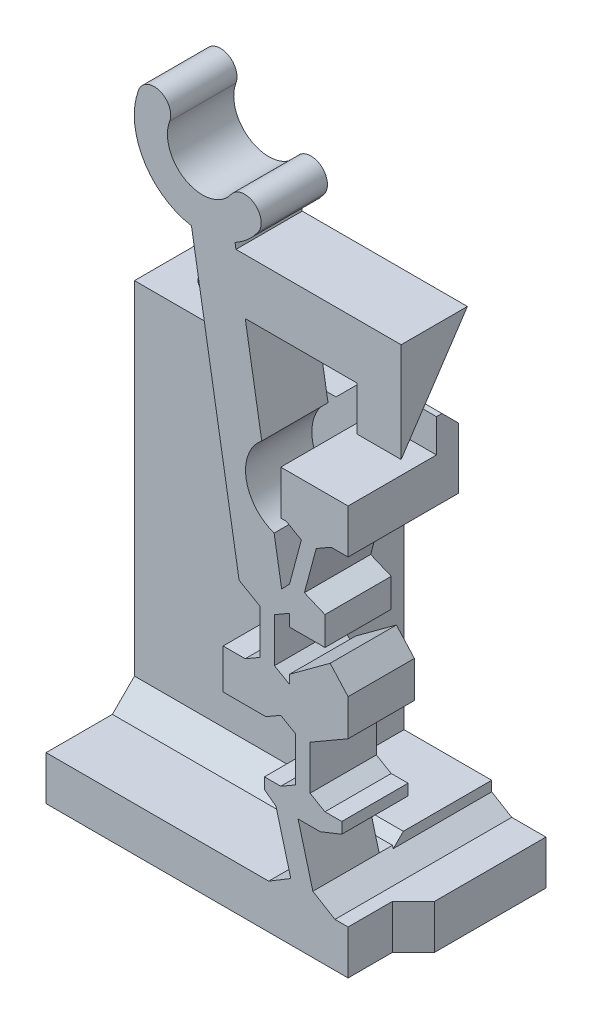
SolidWorks part; units mm, degrees
material "Nylon 6/12"
ref_plane "Front Plane" through (0, 0, 0) normal (0, 0, 1) x (1, 0, 0)
ref_plane "Top Plane" through (0, 0, 0) normal (0, 1, 0) x (1, 0, 0)
ref_plane "Right Plane" through (0, 0, 0) normal (1, 0, 0) x (0, 0, -1)
sketch "Sketch-SkeletonConfigUp" plane through (0, 0, 0) normal (0, 0, 1) x (1, 0, 0)
  line L0 (0, 0) -> (0, -50000) construction
  line L1 (0, 0) -> (4.5811, 6.2164) construction
  line L2 (9.8143, 13.3177) -> (4.5811, 13.945) construction
  line L3 (4.5811, 13.945) -> (2.9713, 10.4094) construction
  line L4 (2.9713, 10.4094) -> (4.5811, 6.2164) construction
  line L5 (4.5811, 13.945) -> (6.2429, 19.1409) construction
  line L6 (2.9713, 10.4094) -> (0.0405, 27.8193) construction
  line L7 (4.5811, 6.2164) -> (9.8143, 13.3177) construction
  line L8 (-587.3593, -797.0242) -> (9.8143, 13.3177) construction
  dimension "D2" = 7.7221
  dimension "D3" = 8.8212
  dimension "D4" = 5.2707
  dimension "D5" = 119.553
  dimension "D6" = 3.8848
  dimension "D7" = 5.4552
  dimension "D8" = 17.6549
  dimension "D9" = 4.4914
  dimension "D10" = 6.745
  dimension "D11" = 145.964
  dimension "D12" = 143.612
sketch "Sketch-SkeletonConfigDown" plane through (0, 0, 0) normal (0, 0, 1) x (1, 0, 0)
  line L0 (0, 0) -> (0, -50000) construction
  line L1 (0, 0) -> (4.5811, 6.2164) construction
  line L2 (9.8143, 13.3177) -> (4.5811, 13.945) construction
  line L3 (4.5811, 13.945) -> (6.1909, 10.4094) construction
  line L4 (6.1909, 10.4094) -> (4.5811, 6.2164) construction
  line L5 (4.5811, 13.945) -> (1.753, 18.6098) construction
  line L6 (6.1909, 10.4094) -> (-8.8652, 19.6294) construction
  line L7 (4.5811, 6.2164) -> (9.8143, 13.3177) construction
  line L8 (-589.9357, -800.5203) -> (9.8143, 13.3177) construction
  dimension "D2" = 7.7221
  dimension "D3" = 8.8212
  dimension "D4" = 5.2707
  dimension "D5" = 119.553
  dimension "D6" = 3.8848
  dimension "D7" = 5.4552
  dimension "D8" = 17.6549
  dimension "D9" = 4.4914
  dimension "D10" = 6.745
  dimension "D11" = 145.964
  dimension "D1" = 143.612
ref_plane "Plane-Cam Base" through (9.128, 0, 0) normal (1, 0, 0) x (0, 0, -1)
ref_plane "Plane-Down-to-Up Derailleur Clearance" through (6.628, 0, 0) normal (1, 0, 0) x (0, 0, -1)
ref_plane "Plane-Cam Cavity Roof" through (5.128, 0, 0) normal (1, 0, 0) x (0, 0, -1)
sketch "Sketch-SwitchBossUp" plane through (0, 0, 0) normal (0, 0, 1) x (1, 0, 0)
  line L0 (3.5811, 11.4759) -> (3.5811, 12.945) construction
  line L5 (5.5811, 12.5552) -> (5.5811, 11.263)
  line L7 (1.5115, 25.1048) -> (1.5536, 24.8548)
  line L8 (-0.4607, 24.7728) -> (1.6966, 11.9577)
  line L9 (2.9713, 10.4094) -> (0.0405, 27.8193) construction
  line L11 (0.1364, 21.2256) -> (2.1086, 21.5576) construction
  line L15 (6.628, -23.7286) -> (6.628, 23.7286) construction
  line L16 (2.9713, 10.4094) -> (4.5811, 6.2164) construction
  line L17 (3.5811, 12.945) -> (3.5811, 14.945) construction
  line L18 (5.5811, 12.945) -> (5.5811, 14.945) construction
  line L19 (4.2561, 13.945) -> (4.9061, 13.945) construction
  line L20 (3.5811, 14.945) -> (5.5811, 14.945) construction
  line L21 (3.5811, 12.945) -> (5.5811, 12.945) construction
  line L22 (4.5811, 12.945) -> (4.5811, 14.945) construction
  line L23 (4.5811, 6.2164) -> (8.5405, 7.1023) construction
  line L24 (1.9713, 9.4094) -> (1.9713, 11.4094) construction
  line L25 (3.9713, 9.4094) -> (3.9713, 11.4094) construction
  line L26 (3.9713, 9.4094) -> (1.9713, 9.4094) construction
  line L27 (1.9713, 11.4094) -> (3.9713, 11.4094) construction
  line L28 (3.5811, 7.2164) -> (5.5811, 7.2164) construction
  line L29 (3.5811, 7.2164) -> (3.5811, 5.2164) construction
  line L30 (5.5811, 7.2164) -> (5.5811, 5.2164) construction
  line L31 (3.5811, 5.2164) -> (5.5811, 5.2164) construction
  line L32 (4.9061, 6.2164) -> (4.2561, 6.2164) construction
  line L40 (3.2963, 10.4094) -> (2.6463, 10.4094) construction
  line L66 (0.0405, 27.8193) -> (0.0405, 50027.8193) construction
  line L76 (5.5811, 11.263) -> (5.5811, 12.5552) construction
  line L77 (5.5811, 7.6061) -> (6.628, 8.2105)
  line L80 (5.8152, 10.763) -> (6.628, 9.8603)
  line L81 (9.128, 1033.2419) -> (9.128, 20.0586) construction
  line L85 (6.9307, 9.5241) -> (8.5405, 7.7363) construction
  line L88 (5.7256, 17.3347) -> (6.628, 17.3347)
  line L92 (3.7762, 8.3129) -> (6.9307, 9.5241) construction
  line L98 (1.9713, 9.0197) -> (0.9713, 9.0197)
  line L99 (0.9713, 9.0197) -> (0.9713, 7.2164)
  line L100 (0.9713, 7.2164) -> (2.9061, 7.2164)
  line L101 (4.5811, 6.2164) -> (6.9307, 9.5241) construction
  line L103 (0.0405, 27.8193) -> (1.9448, 26.4638) construction
  line L104 (6.9307, 9.5241) -> (8.5405, 7.7363) construction
  line L107 (1.9713, 9.4094) -> (1.9713, 9.0197) construction
  line L109 (0.0405, 27.8193) -> (-2.1498, 28.6358) construction
  line L111 (6.628, 9.8603) -> (6.628, 8.2105)
  line L112 (6.628, 9.8603) -> (6.9307, 9.5241) construction
  line L113 (2.8424, 4.8267) -> (2.8424, 4.3267)
  line L114 (7.3693, 7.7363) -> (7.3563, 7.7363) construction
  line L121 (5.0345, -1.1653) -> (5.0345, 1.437) construction
  line L122 (9.028, 22.3548) -> (9.028, 20.3548)
  line L127 (5.5811, 15.3347) -> (5.5811, 14.945) construction
  line L130 (6.0345, 0.8347) -> (6.628, 0.8347)
  line L132 (2.8424, 4.3267) -> (3.3646, 3.937)
  line L133 (2.9713, 10.4094) -> (6.1909, 10.4094) construction
  line L134 (4.5811, 10.4094) -> (4.5811, 13.945) construction
  line L135 (4.5811, 10.4094) -> (4.5811, 6.2164) construction
  line L137 (3.9713, 9.4094) -> (5.5811, 7.2164) construction
  line L139 (5.8152, 10.763) -> (3.9713, 9.4094)
  line L141 (4.0345, 1.437) -> (3.0345, 0.8347)
  line L142 (3.0345, 0.8347) -> (3.0345, -1.1653)
  line L143 (9.128, 20.0586) -> (9.128, 18.3333) construction
  line L145 (9.128, 16.6071) -> (9.128, -49992.4167) construction
  line L147 (5.5811, 11.263) -> (5.5811, 12.5552) construction
  line L150 (3.0345, -1.1653) -> (5.0345, -1.1653)
  line L151 (3.3646, 3.937) -> (4.3646, 3.937) construction
  line L152 (4.5126, 14.945) -> (3.9767, 12.945)
  line L153 (5.1855, 14.945) -> (4.6496, 12.945)
  line L157 (3.5811, 17.3347) -> (3.5811, 15.3347)
  line L158 (5.8605, 15.3347) -> (6.628, 15.3347)
  line L162 (3.2963, 11.4094) -> (3.2963, 9.4094)
  line L164 (2.6463, 11.4094) -> (2.6463, 9.4094)
  line L169 (4.2561, 7.2164) -> (4.2561, 5.2164)
  line L170 (4.9061, 5.2164) -> (4.9061, 7.2164)
  line L175 (4.2561, 7.2164) -> (3.5811, 7.6061)
  line L176 (4.9061, 7.2164) -> (5.5811, 7.6061)
  line L177 (5.5811, 7.2164) -> (5.5811, 7.6061) construction
  line L179 (4.2561, 5.2164) -> (3.5811, 4.8267)
  line L180 (3.5811, 5.2164) -> (3.5811, 4.8267) construction
  line L181 (3.5811, 4.8267) -> (2.8424, 4.8267)
  line L183 (4.9061, 5.2164) -> (5.5811, 4.8267)
  line L184 (5.5811, 5.2164) -> (5.5811, 4.8267) construction
  line L186 (9.128, -23.7286) -> (9.128, 23.7286) construction
  line L187 (2.6463, 9.4094) -> (1.9713, 9.0197)
  line L188 (3.2963, 9.4094) -> (3.9713, 9.0197)
  line L189 (3.2963, 11.4094) -> (3.9713, 11.7991)
  line L190 (2.6463, 11.4094) -> (1.6966, 11.9577)
  line L191 (3.9713, 11.4094) -> (3.9713, 11.7991) construction
  line L192 (3.9713, 11.7991) -> (3.9713, 11.263)
  line L193 (4.6496, 12.945) -> (5.5811, 12.5552)
  line L194 (3.9767, 12.945) -> (3.6203, 12.5779)
  line L195 (3.9713, 11.263) -> (5.5811, 11.263)
  line L196 (3.9713, 9.4094) -> (3.9713, 9.0197)
  line L197 (3.5811, 7.2164) -> (3.5811, 7.6061) construction
  line L199 (3.5811, 7.6061) -> (2.9061, 7.2164)
  line L201 (2.8424, 4.3267) -> (2.8424, 3.937) construction
  line L202 (2.8424, 3.937) -> (3.3646, 3.937) construction
  line L204 (5.0345, 1.437) -> (3.0345, 1.437) construction
  line L205 (3.0345, 1.437) -> (3.0345, 0.8347) construction
  line L206 (5.0345, 1.437) -> (6.0345, 0.8347)
  line L207 (9.128, 18.3333) -> (9.128, 16.6071) construction
  line L208 (6.628, -1.1653) -> (6.628, 0.8347)
  line L209 (9.128, 20.0586) -> (9.128, 16.6071) construction
  line L211 (5.0345, 1.437) -> (4.3646, 3.937)
  line L212 (4.0345, 1.437) -> (3.3646, 3.937)
  line L214 (4.5126, 14.945) -> (3.8375, 15.3347)
  line L215 (3.8375, 15.3347) -> (3.5811, 15.3347)
  line L216 (5.1855, 14.945) -> (5.8605, 15.3347)
  line L217 (5.5811, 12.945) -> (5.5811, 12.5552) construction
  line L218 (5.1855, 14.945) -> (5.1855, 15.3347) construction
  line L219 (5.8605, 15.3347) -> (3.8375, 15.3347) construction
  line L221 (9.028, 22.3548) -> (9.028, 24.8548)
  line L224 (3.5811, 17.3347) -> (5.7256, 17.3347)
  line L232 (6.628, 15.3347) -> (6.628, 17.3347)
  line L233 (6.628, -1.1653) -> (5.0345, -1.1653)
  line L236 (1.5536, 24.8548) -> (9.028, 24.8548)
  line L240 (4.3646, 3.937) -> (5.3646, 3.937)
  line L241 (5.3646, 3.937) -> (6.3424, 4.3267)
  line L248 (7.028, 22.3548) -> (1.9744, 22.3548)
  line L249 (1.9744, 22.3548) -> (2.7198, 17.9273)
  line L250 (9.028, 20.3548) -> (7.028, 20.3548)
  line L251 (7.028, 20.3548) -> (7.028, 22.3548)
  line L252 (3.2801, 14.5986) -> (3.6203, 12.5779)
  line L253 (4.2672, 14.0291) -> (4.895, 13.8608) construction
  line L367 (5.5811, 4.8267) -> (6.3424, 4.8267)
  line L368 (6.3424, 4.8267) -> (6.3424, 4.3267)
  arc A0 (1.5115, 25.1048) -> (2.5558, 26.0289) centre (0.0405, 27.8193) ccw
  arc A1 (-0.4607, 24.7728) -> (-2.8525, 28.8978) centre (0.0405, 27.8193) cw
  arc A2 (-2.8525, 28.8978) -> (-1.447, 28.3738) centre (-2.1498, 28.6358) cw
  arc A3 (2.5558, 26.0289) -> (1.3338, 26.8987) centre (1.9448, 26.4638) ccw
  arc A4 (-1.447, 28.3738) -> (1.3338, 26.8987) centre (0.0405, 27.8193) ccw
  arc A5 (3.5811, 12.945) -> (3.5811, 14.945) centre (3.1778, 13.945) ccw construction
  arc A6 (5.5811, 12.945) -> (5.5811, 14.945) centre (5.9843, 13.945) cw construction
  arc A7 (2.5293, 9.921) -> (1.9713, 11.4094) centre (1.568, 10.4094) ccw construction
  arc A8 (3.9713, 11.4094) -> (3.9713, 9.4094) centre (4.3745, 10.4094) ccw construction
  arc A9 (3.5811, 7.2164) -> (3.5811, 5.2164) centre (3.1779, 6.2164) cw construction
  arc A10 (5.5811, 7.2164) -> (5.5811, 5.2164) centre (5.9844, 6.2164) ccw construction
  circle A28 centre (0.0405, 27.8193) radius 2.3375 construction
  arc A29 (1.9713, 9.4094) -> (2.5293, 9.921) centre (1.568, 10.4094) ccw construction
  arc A30 (3.2801, 14.5986) -> (2.7198, 17.9273) centre (3.9114, 16.4164) cw
  point P53 (4.5811, 13.945)
  point P63 (2.9713, 10.4094)
  point P80 (0, 0)
  point P83 (0, 0)
  point P93 (1.1225, 21.3916)
  dimension "D23" = 1.5875
  dimension "D24" = 0.75
  dimension "D2" = 2
  dimension "D5" = 2
  dimension "D8" = 42
  dimension "D16" = 42
  dimension "D27" = 120
  dimension "D28" = 120
  dimension "D29" = 120
  dimension "D30" = 120
  dimension "D31" = 120
  dimension "D32" = 120
  dimension "D33" = 120
  dimension "D34" = 120
  dimension "D17" = 0.5
  dimension "D21" = 2
  dimension "D22" = 1
  dimension "D38" = 2
  dimension "D39" = 0.5
  dimension "D40" = 60
  dimension "D41" = 1
  dimension "D42" = 45
  dimension "D43" = 120
  dimension "D10" = 15
  dimension "D12" = 2.5
  dimension "D13" = 1
  dimension "D19" = 1
  dimension "D25" = 15
  dimension "D26" = 120
  dimension "D35" = 120
  dimension "D20" = 3
  dimension "D48" = 2
  dimension "D82" = 1
  dimension "D83" = 3.5
  dimension "D14" = 2.5
  dimension "D15" = 0.25
  dimension "D7" = 2
  dimension "D9" = 2
  dimension "D6" = 0.65
extrude "Boss-Switch Body" add sketch "Sketch-SwitchBossUp" along normal blind 3
sketch "Sketch1" plane through (0, 0, 0) normal (0, 0, -1) x (-1, 0, 0)
  line L1 (-7.5811, -1.1653) -> (0.4122, -1.1653)
  line L2 (-7.5811, -1.1653) -> (-7.5811, 0.8347)
  line L4 (0.4122, -1.1653) -> (0.4122, 0.8347)
  line L5 (-3.5811, 18.8347) -> (-7.5811, 18.8347)
  line L10 (-7.5811, 18.8347) -> (-7.5811, 15.3347)
  line L11 (-4.0345, 1.437) -> (-5.0345, 1.437)
  line L12 (-7.5811, 15.3347) -> (-3.5811, 15.3347)
  line L13 (-4.0345, 1.437) -> (-3.0345, 0.8347)
  line L14 (-3.5811, 15.3347) -> (-3.5811, 18.8347)
  line L20 (-4.3646, 3.937) -> (-5.0345, 1.437) construction
  line L22 (-3.0345, -1.1653) -> (-6.628, -1.1653) construction
  line L23 (-3.0345, 0.8347) -> (0.4122, 0.8347)
  line L24 (-5.0345, 1.437) -> (-6.0345, 0.8347)
  line L25 (-6.0345, 0.8347) -> (-7.5811, 0.8347)
  dimension "D1" = 3.5
extrude "Boss-Flange Width" add sketch "Sketch1" along normal blind 5
ref_plane "Plane-Sta2Sit Groove" through (0.0405, 0, 0) normal (1, 0, 0) x (0, 0, -1)
ref_plane "Plane-Cam Outer Surface" through (-12.0395, 0, 0) normal (1, 0, 0) x (0, 0, -1)
ref_plane "Plane-FlangeTop" through (-7.0395, 0, 0) normal (1, 0, 0) x (0, 0, -1)
sketch "Sketch2" plane through (-7.0395, 0, 0) normal (1, 0, 0) x (0, 0, -1)
  line L0 (5, 15.3347) -> (-3, 15.3347) construction
  line L1 (5, 17.3347) -> (1, 17.3347)
  line L2 (5, 17.3347) -> (5, 15.3347)
  line L3 (5, 15.3347) -> (1, 15.3347)
  line L4 (1, 17.3347) -> (1, 15.3347)
  line L5 (-3, -1.1653) -> (-3, 0.8347) construction
  line L11 (5, 0.8347) -> (-3, 0.8347)
  line L12 (5, 0.8347) -> (5, -1.1653)
  line L13 (5, -1.1653) -> (-3, -1.1653)
  line L14 (-3, 0.8347) -> (-3, -1.1653)
  line L15 (0, 10.4094) -> (0, 27.8193) construction
  line L17 (5, 0.8347) -> (5, -1.1653) construction
  line L18 (-3, 0.8347) -> (0, 0.8347) construction
  dimension "D1" = 1
  dimension "D2" = 2
extrude "Boss-Flange Height" add sketch "Sketch2" along normal up to surface (11.6675 mm away)
sketch "Sketch10" plane through (0, 15.3347, 0) normal (0, 1, 0) x (1, 0, 0)
  line L0 (9.128, -23.7286) -> (9.128, 23.7286) construction
  line L1 (7.5811, 5) -> (5.128, 5)
  line L2 (7.5811, 5) -> (7.5811, 2)
  line L3 (7.5811, 2) -> (5.128, 2)
  line L5 (4.628, 7) -> (4.628, 1) construction
  line L6 (3.5811, 1) -> (-7.0395, 1) construction
  line L8 (5.128, 5) -> (5.128, 2)
  dimension "D1" = 1
  dimension "D2" = 0.5
  dimension "D3" = 4.5
extrude "Cut-Up-To-Down Derailleur Clearance" cut sketch "Sketch10" along normal up to next
sketch "Sketch17" plane through (0, 15.3347, 0) normal (0, -1, 0) x (1, 0, 0)
  line L0 (5.128, -5) -> (-7.0395, -5)
  line L1 (5.128, -5) -> (-7.0395, -5) construction
  line L2 (-7.0395, -5) -> (-7.0395, -1)
  line L3 (-7.0395, -1) -> (5.128, -1)
  line L4 (5.128, -1) -> (5.128, -5)
  line L5 (-7.0395, -1) -> (-7.0395, -5) construction
extrude "Boss-Flange Support" add sketch "Sketch17" along normal up to surface (14.5 mm away) up to face at (-2.0025, 0.8347, -1)
sketch "Sketch-HolePositions" plane through (0, -1.1653, 0) normal (0, -1, 0) x (1, 0, 0)
  line L0 (-7.0395, -3) -> (7.5811, -3) construction
  line L1 (7.5811, -5) -> (-7.0395, -5) construction
  line L2 (7.5811, -5) -> (7.5811, 0) construction
  line L4 (-7.0395, -22.2167) -> (-7.0395, 22.2167) construction
  point P6 (-5.0395, -3)
  point P7 (-0.5395, -3)
  dimension "D1" = 2
  dimension "D2" = 4.5
  dimension "D3" = 2
sketch "Sketch6" plane through (0, -1.1653, 0) normal (0, -1, 0) x (-1, 0, 0)
  point P0 (5.0395, 3)
  point P3 (0.5395, 3)
hole_wizard "Tap Drill for M2x0.4 Tap1" positions "Sketch6" profile "Sketch5" hole size "M2x0.4" standard "ANSI Metric" end condition through all
sketch "Sketch5" plane through (-5.0395, -1.1653, -3) normal (1, 0, 0) x (0, 0, -1)
  line L0 (0, 0) -> (0, 30.5511)
  line L1 (0, 30.5511) -> (0.8, 30.5511)
  line L2 (0.8, 30.5511) -> (0.8, 0)
  line L5 (0.8, 0) -> (0, 0)
  line L11 (0, -6.35) -> (0, 107.95) construction
  dimension "Thru Hole Dia." = 1.6
  dimension "Thru Hole Depth" = 30.5511
sketch "Sketch9" plane through (0, -1.1653, 0) normal (0, -1, 0) x (1, 0, 0)
  point P0 (-5.0395, -3)
  point P3 (-0.5395, -3)
hole_wizard "M2 Clearance Hole2" positions "Sketch9" profile "Sketch8" hole size "M2" standard "ANSI Metric"
sketch "Sketch8" plane through (-5.0395, -1.1653, -3) normal (1, 0, 0) x (0, 0, -1)
  line L0 (0, 0) -> (0, 15.721)
  line L1 (0, 15.721) -> (1.2, 15)
  line L2 (1.2, 15) -> (1.2, 0)
  line L5 (1.2, 0) -> (0, 0)
  line L10 (0, 15.721) -> (-1.2, 15) construction
  line L11 (0, -6.35) -> (0, 107.95) construction
  dimension "Hole Dia." = 2.4
  dimension "Hole Depth" = 15
  dimension "Drill Angle" = 118
sketch "Sketch-Measurements for Derailleur Ramps" [suppressed] plane through (0, 0, 0) normal (0, 0, 1) x (1, 0, 0)
  line L0 (3.184, 15.1695) -> (2.4687, 19.4188)
  line L1 (2.8264, 17.2941) -> (1.8402, 17.1281)
  line L2 (2.9713, 10.4094) -> (0.0405, 27.8193) construction
  line L3 (1.8402, 17.1281) -> (-1.3081, 15.0016)
  line L4 (6.1909, 10.4094) -> (-8.8652, 19.6294) construction
  line L5 (1.8402, 17.1281) -> (2.6012, 12.6077)
  line L6 (2.6012, 12.6077) -> (-1.3081, 15.0016)
  line L7 (0.2661, 16.0649) -> (0.2661, 17.1281)
  line L8 (0.2661, 17.1281) -> (1.8402, 17.1281)
  line L9 (6.1909, 10.4094) -> (2.9713, 10.4094)
  line L10 (5.386, 8.3129) -> (3.7762, 8.3129)
  line L11 (2.6116, 18.5698) -> (1.5115, 25.1048) construction
  line L12 (6.1909, 10.4094) -> (4.5811, 6.2164) construction
  line L13 (4.5811, 8.3129) -> (4.5811, 8.7912)
  line L14 (4.5811, 6.2164) -> (5.386, 8.3129)
  line L15 (2.9713, 10.4094) -> (4.5811, 6.2164) construction
  line L16 (3.7762, 8.3129) -> (4.5811, 6.2164)
  line L17 (5.386, 8.3129) -> (5.386, 8.7912)
  dimension "D1" = 1.5742
  dimension "D2" = 0.8049
ref_plane "Plane1" through (0, 7.1023, 0) normal (0, 1, 0) x (1, 0, 0)
ref_plane "Plane-Cantilever Cut" [suppressed] through (7.0848, 8.5204, -1.9058) normal (-0.6301, -0.7578, 0.1695) x (-0.7765, 0.6151, -0.1368)
sketch "Sketch14" [suppressed] plane through (7.0848, 8.5204, -1.9058) normal (-0.6301, -0.7578, 0.1695) x (-0.7765, 0.6151, -0.1368)
  line L0 (2.3023, -1.6911) -> (-0.3551, -1.6911)
  line L2 (2.3023, -4.3362) -> (2.3023, -1.6911)
  line L3 (-0.3551, -1.6911) -> (-0.3551, -4.4608)
  line L5 (-0.3551, -4.4608) -> (1.0087, -5.0843)
  line L6 (1.0087, -5.0843) -> (2.3023, -4.3362)
extrude "Cut-Down-to-Up Cantilever Slope" [suppressed] cut sketch "Sketch14" against normal up to next
ref_plane "Plane-Symmetry Plane" through (0, 0, 1.5) normal (0, 0, 1) x (1, 0, 0)
sketch "Sketch-Cable Center Point" plane through (0, 0, 1.5) normal (0, 0, 1) x (1, 0, 0)
  line L0 (0.0405, 27.8193) -> (0.1722, 27.0366)
  line L1 (2.9713, 10.4094) -> (0.0405, 27.8193) construction
  point P0 (0.0405, 27.8193)
  dimension "D1" = 0.7937
chamfer "Chamfer-Flange Support" distance 1.5 angle 45 1 edges at (3.5811, 17.3347, -3)
chamfer "Chamfer-Flange Support 2" distance 1.5 angle 45 2 edges at (5.128, 17.0847, -2) (5.128, 15.3347, -1.5)
chamfer "Chamfer-Flange Support 3" distance 1 angle 45 1 edges at (-2.0025, 0.8347, -1)
chamfer "Chamfer7" [suppressed] distance 1 angle 45
sketch "Sketch23" plane through (0, 0, -1) normal (0, 0, 1) x (1, 0, 0)
  line L0 (5.128, 1.8347) -> (1.1605, 1.8347)
  line L1 (-7.0395, 1.8347) -> (5.128, 1.8347) construction
  line L2 (1.1605, 1.8347) -> (1.1605, 13.8347)
  line L3 (1.1605, 13.8347) -> (5.128, 13.8347)
  line L4 (5.128, 13.8347) -> (5.128, 1.8347)
  line L5 (0.6605, -1.1653) -> (0.6605, 13.8347) construction
  dimension "D1" = 0.5
extrude "Cut-Gap for Printing" cut sketch "Sketch23" against normal through all
sketch "Sketch25" plane through (0, 0, 0) normal (0, 0, 1) x (1, 0, 0)
  line L0 (6.628, 15.3347) -> (7.5811, 15.3347)
  line L1 (7.5811, 15.3347) -> (7.5811, 18.8347)
  line L2 (7.5811, 18.8347) -> (6.628, 18.8347)
  line L3 (6.628, -23.7286) -> (6.628, 23.7286) construction
  line L4 (7.5811, 18.8347) -> (3.5811, 18.8347) construction
  line L5 (6.628, 18.8347) -> (6.628, 15.3347)
  line L6 (7.5811, 18.8347) -> (7.5811, 15.3347) construction
extrude "Cut-Derailleur Clearance" cut sketch "Sketch25" against normal through all
chamfer "Chamfer8" distance 1 angle 45 1 edges at (6.628, -0.1653, 0)
ref_plane "Plane2" through (-3.0866, 5.589, 8.3835) normal (0.2929, -0.5304, -0.7956) x (-0.9561, -0.1625, -0.2437)
sketch "Sketch26" plane through (-3.0866, 5.589, 8.3835) normal (0.2929, -0.5304, -0.7956) x (-0.9561, -0.1625, -0.2437)
  line L0 (-7.553, 20.6804) -> (-7.553, 14.9094)
  line L1 (-12.6703, 20.6804) -> (-5.5238, 20.6804) construction
  line L3 (-7.553, 14.9094) -> (-20.0302, 14.9094)
  line L4 (-20.0302, 14.9094) -> (-20.0302, 20.6804)
  line L5 (-20.0302, 20.6804) -> (-7.553, 20.6804)
extrude "Cut-Up-to-Down Cantilever Slope" cut sketch "Sketch26" along normal up to next
sketch "Sketch27" plane through (5.128, 0, 0) normal (1, 0, 0) x (0, 0, -1)
  line L0 (3.5, 18.8347) -> (3.5, 13.8347) construction
  line L1 (2.5, 18.8347) -> (5, 18.8347)
  line L2 (2.5, 18.8347) -> (2.5, 13.8347)
  line L3 (2.5, 13.8347) -> (5, 13.8347)
  line L4 (5, 18.8347) -> (5, 13.8347)
  dimension "D1" = 1
extrude "Cut-Wide Derailleur Clearance" cut sketch "Sketch27" against normal blind 4 and the other way through all
chamfer "Chamfer9" distance 1.25 angle 45 1 edges at (4.8545, 18.8347, -2.5)
sketch "Sketch28" plane through (0, 0, -1) normal (0, 0, 1) x (1, 0, 0)
  line L0 (3.5811, 18.8347) -> (6.628, 18.8347)
  line L1 (6.628, 18.8347) -> (6.628, 17.3347)
  line L2 (6.628, 17.3347) -> (3.5811, 17.3347)
  line L3 (3.5811, 17.3347) -> (3.5811, 18.8347)
extrude "Cut-Extrude1" cut sketch "Sketch28" along normal up to surface (1 mm away) up to face at (5.1045, 18.0847, 0)
equation "\"axle-diameter\"=2"
equation "\"switch-thickness\"=12"
equation "\"base-width\"=4.0"
equation "\"axle-bushing-radius\"=3"
equation "\"clearance\"= 0.25"
equation "\"arm-width\"=1.5"
equation "\"min-diameter\"=70"
equation "\"alpha\"=143.6120"
equation "\"gamma\"=119.5526"
equation "\"delta\"=145.9637"
equation "\"epsilon\"=6.7452"
equation "\"l_AB\"=8.8212"
equation "\"l_AC\"=4.4914"
equation "\"l_BD\"=5.2707"
equation "\"l_CD\"=3.8848"
equation "\"l_CE\"=17.6549"
equation "\"l_DF\"=5.4552"
equation "\"l_OA\"=7.7221"
equation "\"D2@Sketch-SkeletonConfigUp\" = \"l_OA\""
equation "\"D3@Sketch-SkeletonConfigUp\" = \"l_AB\""
equation "\"D4@Sketch-SkeletonConfigUp\" = \"l_BD\""
equation "\"D5@Sketch-SkeletonConfigUp\" = \"gamma\""
equation "\"D6@Sketch-SkeletonConfigUp\" = \"l_CD\""
equation "\"D7@Sketch-SkeletonConfigUp\" = \"l_DF\""
equation "\"D8@Sketch-SkeletonConfigUp\" = \"l_CE\""
equation "\"D9@Sketch-SkeletonConfigUp\" = \"l_AC\""
equation "\"D_groove\"=3.175"
equation "\"D7@Sketch-SkeletonConfigDown\" = \"l_DF\""
equation "\"D6@Sketch-SkeletonConfigDown\" = \"l_CD\""
equation "\"D2@Sketch-SkeletonConfigDown\" = \"l_OA\""
equation "\"D3@Sketch-SkeletonConfigDown\" = \"l_AB\""
equation "\"D9@Sketch-SkeletonConfigDown\" = \"l_AC\""
equation "\"D8@Sketch-SkeletonConfigDown\" = \"l_CE\""
equation "\"D5@Sketch-SkeletonConfigDown\" = \"gamma\""
equation "\"D4@Sketch-SkeletonConfigDown\" = \"l_BD\""
equation "\"D1@Sketch-SkeletonConfigDown\" = \"alpha\""
equation "\"hinge_length\"=1.5"
equation "\"hinge_depth\"=0.25"
equation "\"D10@Sketch-SkeletonConfigUp\"=\"epsilon\""
equation "\"D11@Sketch-SkeletonConfigUp\"=\"delta\""
equation "\"D12@Sketch-SkeletonConfigUp\"=\"alpha\""
equation "\"D11@Sketch-SkeletonConfigDown\"=\"delta\""
equation "\"D10@Sketch-SkeletonConfigDown\"=\"epsilon\""
equation "\"EE_dx\"=8.9056"
equation "\"EE_dy\"=8.1898"
equation "\"r_groove\"=\"D_groove\"/2"
equation "\"t_wall\"=25.4/16"
equation "\"width_lower\"=\"D_groove\"+\"t_wall\""
equation "\"cable_to_bottom\"=30.6257"
equation "\"switch_EE-up_base_dy\"=24"
equation "\"switch_EE-down_base_dy\"=16"
equation "\"D_axle\"=25.4/8"
equation "\"D_up_to_down\"=16"
equation "\"D_down_to_up\"=25"
equation "\"t_cam_base\"=7.5"
equation "\"D23@Sketch-SwitchBossUp\"=\"D_groove\"/2"
equation "\"D1@Sketch-Cable Center Point\"=\"D_groove\"/4"
